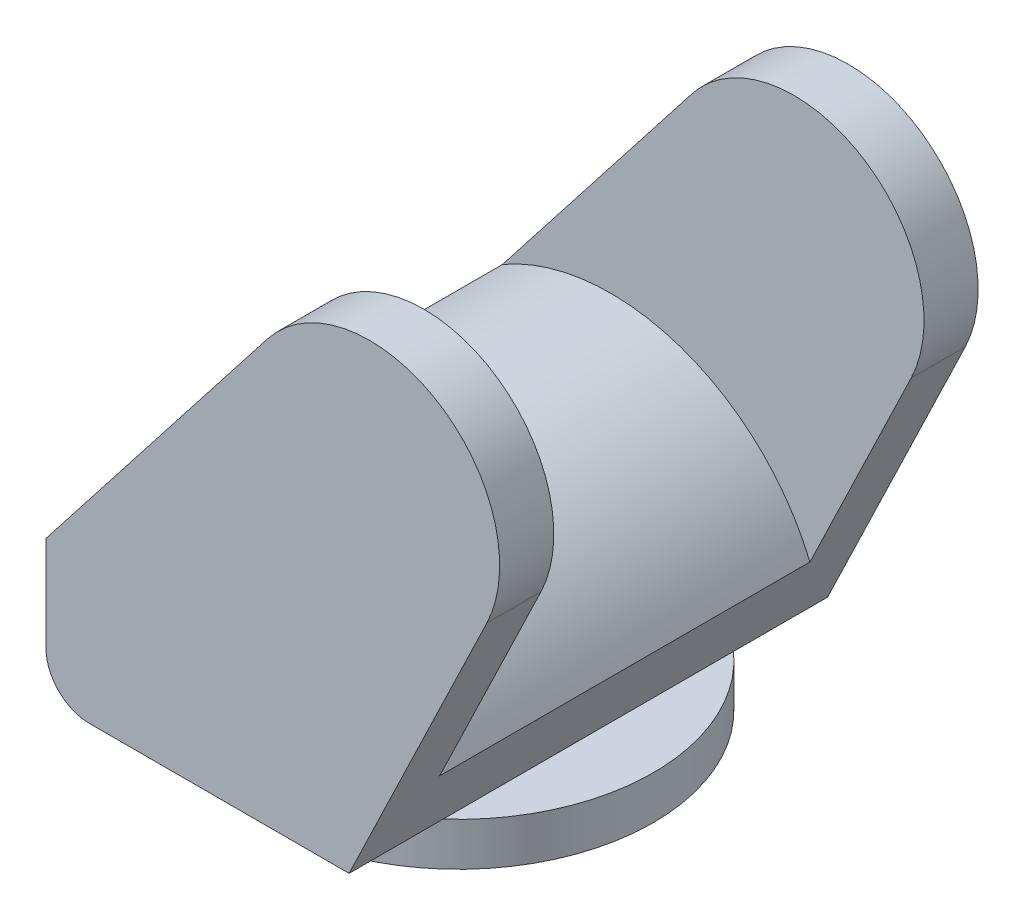
SolidWorks part; units mm, degrees
ref_plane "Front Plane" through (0, 0, 0) normal (0, 0, 1) x (1, 0, 0)
ref_plane "Top Plane" through (0, 0, 0) normal (0, 1, 0) x (1, 0, 0)
ref_plane "Right Plane" through (0, 0, 0) normal (1, 0, 0) x (0, 0, -1)
sketch "Sketch1" plane through (0, 0, 0) normal (1, 0, 0) x (0, 0, -1)
  line L0 (-64.2929, -51.1093) -> (55.7071, -51.1093)
  line L1 (75.7071, -31.1093) -> (75.7071, 12.8907)
  line L2 (75.7071, 12.8907) -> (-26.5576, 143.7893)
  line L3 (-64.2929, -51.1093) -> (-127.8857, 80.7938)
  arc A0 (-26.5576, 143.7893) -> (-127.8857, 80.7938) centre (-73.839, 106.8507) ccw
  arc A1 (75.7071, -31.1093) -> (55.7071, -51.1093) centre (55.7071, -31.1093) cw
  dimension "D1" = 20
  dimension "D3" = 120
  dimension "D2" = 120
  dimension "D4" = 44
  dimension "D5" = 157.96
  dimension "D6" = 166.11
extrude "Boss-Extrude1" add sketch "Sketch1" along normal blind 110.5 and the other way blind 110.5
sketch "Sketch2" plane through (0, 0, 0) normal (1, 0, 0) x (0, 0, -1)
  line L0 (-127.8857, 80.7938) -> (-64.2929, -51.1093) construction
  line L1 (75.7071, 12.8907) -> (-26.5576, 143.7893) construction
  line L2 (-127.8857, 80.7938) -> (-81.1498, -16.1449)
  line L3 (60.8576, 31.898) -> (-26.5576, 143.7893)
  arc A0 (-26.5576, 143.7893) -> (-127.8857, 80.7938) centre (-73.839, 106.8507) ccw construction
  arc A1 (-26.5576, 143.7893) -> (-127.8857, 80.7938) centre (-73.839, 106.8507) ccw
  arc A2 (60.8576, 31.898) -> (-81.1498, -16.1449) centre (10.8457, -54.1718) ccw
extrude "Cut-Extrude1" cut sketch "Sketch2" against normal blind 85.5 and the other way blind 85.5 contours A1 L2 A2 L3
sketch "Sketch3" plane through (0, -51.1093, 0) normal (0, -1, 0) x (1, 0, 0)
  line L0 (-110.5, 64.2929) -> (110.5, 64.2929) construction
  circle A0 centre (0, 4.2929) radius 90
  dimension "D1" = 180
  dimension "D2" = 60
extrude "Boss-Extrude2" add sketch "Sketch3" along normal blind 20 contours A0
move or copy body "Body-Move/Copy1" bodies to move or copy 103 copy no rotation origin (0, 0, 0) rotation axis (0, 1, 0) rotation angle 90
sketch "Sketch4" [suppressed] plane through (0, 0, 110.5) normal (0, 0, 1) x (1, 0, 0)
  text T0 "HAJ" font "Century Gothic" height 25
extrude "Boss-Extrude3" [suppressed] add sketch "Sketch4" along normal blind 5
